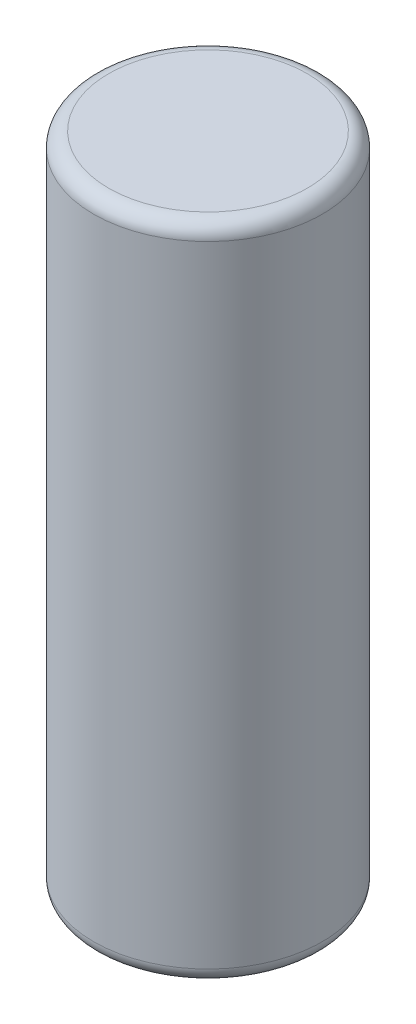
SolidWorks part; units mm, degrees
ref_plane "Front Plane" through (0, 0, 0) normal (0, 0, 1) x (1, 0, 0)
ref_plane "Top Plane" through (0, 0, 0) normal (0, 1, 0) x (1, 0, 0)
ref_plane "Right Plane" through (0, 0, 0) normal (1, 0, 0) x (0, 0, -1)
sketch "Sketch2" plane through (0, 0, 0) normal (0, 1, 0) x (1, 0, 0)
  circle A0 centre (0, 0) radius 76.2
  dimension "D1" = 152.4
extrude "Boss-Extrude1" add sketch "Sketch2" along normal blind 440
fillet "Fillet1" radius 10 2 edges at (0, 0, 76.2) (0, 440, 76.2)
